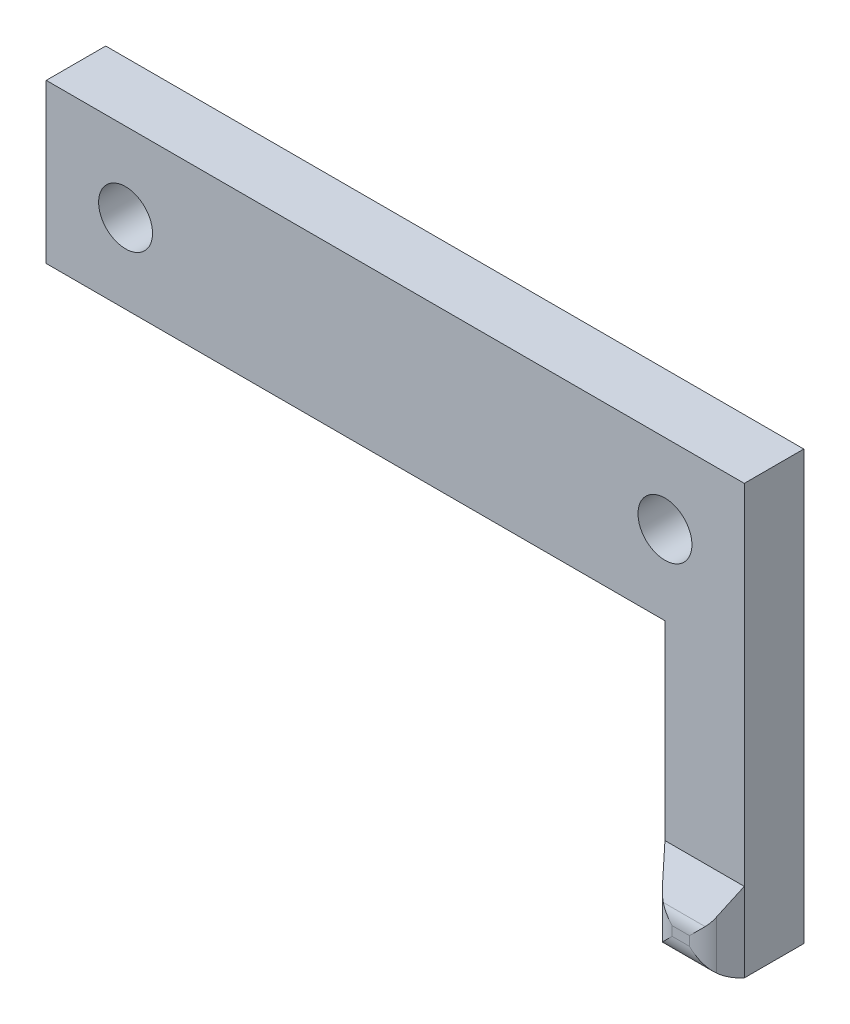
SolidWorks part; units mm, degrees
ref_plane "Front Plane" through (0, 0, 0) normal (0, 0, 1) x (1, 0, 0)
ref_plane "Top Plane" through (0, 0, 0) normal (0, 1, 0) x (1, 0, 0)
ref_plane "Right Plane" through (0, 0, 0) normal (1, 0, 0) x (0, 0, -1)
sketch "Sketch1" plane through (0, 0, 0) normal (0, 0, 1) x (1, 0, 0)
  line L0 (0, 0) -> (68, 0) construction
  line L2 (78, 10) -> (-10, 10)
  line L3 (78, 10) -> (78, -10)
  line L4 (78, -10) -> (-10, -10)
  line L5 (-10, 10) -> (-10, -10)
  line L6 (78, 10) -> (-10, -10) construction
  line L7 (78, -10) -> (-10, 10) construction
  circle A0 centre (0, 0) radius 3.4
  circle A1 centre (68, 0) radius 3.4
  point P5 (34, 0)
  dimension "D2" = 6.8
  dimension "D3" = 10
  dimension "D1" = 68
  dimension "D4" = 10
extrude "Boss-Extrude1" add sketch "Sketch1" along normal blind 7.5
sketch "Sketch2" plane through (0, -10, 0) normal (0, -1, 0) x (1, 0, 0)
  line L0 (68, 0) -> (78, 0)
  line L1 (78, 0) -> (78, 7.5)
  line L2 (-10, 7.5) -> (78, 7.5) construction
  line L3 (78, 7.5) -> (68, 7.5)
  line L4 (68, 7.5) -> (68, 0)
  line L5 (78, 7.5) -> (78, 0) construction
  dimension "D1" = 10
extrude "Boss-Extrude2" add sketch "Sketch2" along normal blind 34
ref_plane "Plane1" through (0, 0, 10.5) normal (0, 0, 1) x (1, 0, 0)
sketch "Sketch3" plane through (0, 0, 10.5) normal (0, 0, 1) x (1, 0, 0)
  line L0 (78, -44) -> (68, -34) construction
  line L2 (68, -34) -> (68, -44) construction
  line L3 (73, -39) -> (73, -44) construction
  line L4 (75.5, -39) -> (70.5, -39)
  line L5 (75.5, -39) -> (75.5, -44)
  line L6 (75.5, -44) -> (70.5, -44)
  line L7 (70.5, -39) -> (70.5, -44)
  line L8 (75.5, -39) -> (70.5, -44) construction
  line L9 (75.5, -44) -> (70.5, -39) construction
  line L10 (78, -44) -> (68, -44) construction
  point P5 (73, -41.5)
  point P13 (73, -39)
  dimension "D1" = 10
  dimension "D2" = 5
sketch "Sketch4" plane through (0, 0, 7.5) normal (0, 0, 1) x (1, 0, 0)
  line L0 (68, -34) -> (78, -44) construction
  line L2 (78, -44) -> (68, -44)
  line L3 (78, -44) -> (78, -34)
  line L4 (78, -34) -> (68, -34)
  line L5 (68, -44) -> (68, -34)
  dimension "D1" = 10
loft "Loft1" add profiles "Sketch4", "Sketch3" connector at (68, -34, 7.5) connector at (70.5, -39, 10.5)
fillet "Fillet1" radius 3 4 edges
